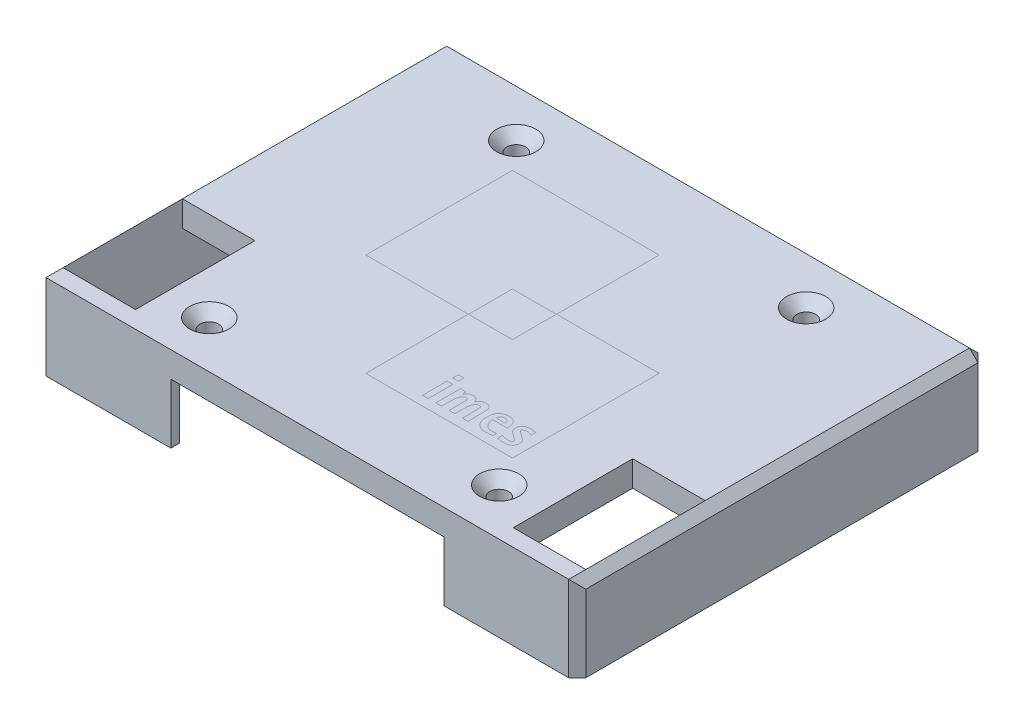
SolidWorks part; units mm, degrees
ref_plane "Front Plane" through (0, 0, 0) normal (0, 0, 1) x (1, 0, 0)
ref_plane "Top Plane" through (0, 0, 0) normal (0, 1, 0) x (1, 0, 0)
ref_plane "Right Plane" through (0, 0, 0) normal (1, 0, 0) x (0, 0, -1)
sketch "Sketch1" plane through (0, 0, 0) normal (0, 1, 0) x (1, 0, 0)
  line L1 (-31.65, -24) -> (31.65, -24)
  line L2 (-31.65, -24) -> (-31.65, 24)
  line L3 (-31.65, 24) -> (31.65, 24)
  line L4 (31.65, -24) -> (31.65, 24)
  line L5 (-31.65, -24) -> (31.65, 24) construction
  line L6 (-31.65, 24) -> (31.65, -24) construction
  line L7 (-17, -18.5) -> (17, -18.5) construction
  line L8 (-17, -18.5) -> (-17, 17.5) construction
  line L9 (-17, 17.5) -> (17, 17.5) construction
  line L10 (17, -18.5) -> (17, 17.5) construction
  line L11 (-17, -18.5) -> (17, 17.5) construction
  line L12 (-17, 17.5) -> (17, -18.5) construction
  point P0 (0, 0)
  point P6 (0, 0)
  point P11 (12.723, -13.4714)
  point P12 (0, -0.5)
  dimension "D1" = 63.3
  dimension "D2" = 48
  dimension "D3" = 36
  dimension "D4" = 34
  dimension "D5" = 0.5
extrude "Boss-Extrude1" add sketch "Sketch1" along normal blind 3
sketch "Sketch2" plane through (0, 0, 0) normal (0, -1, 0) x (1, 0, 0)
  line L0 (-16, 24) -> (-16, 23)
  line L1 (-31.65, 24) -> (31.65, 24) construction
  line L2 (-16, 23) -> (-30.65, 23)
  line L3 (-30.65, 23) -> (-30.65, -23)
  line L4 (-30.65, -23) -> (30.65, -23)
  line L5 (30.65, -23) -> (30.65, 23)
  line L6 (30.65, 23) -> (16, 23)
  line L7 (16, 23) -> (16, 24)
  line L8 (16, 24) -> (31.65, 24)
  line L9 (31.65, 24) -> (31.65, -24) construction
  line L10 (31.65, 24) -> (31.65, -24)
  line L11 (31.65, -24) -> (-31.65, -24)
  line L12 (-31.65, -24) -> (-31.65, 24)
  line L13 (-31.65, 24) -> (-16, 24)
  line L14 (-30.65, 23) -> (-31.65, 23) construction
  line L15 (30.65, 23) -> (31.65, 23) construction
  line L16 (-30.65, -23) -> (-30.65, -24) construction
  point P4 (-16.5638, 19.6362)
  dimension "D1" = 1
  dimension "D2" = 32
extrude "Boss-Extrude2" add sketch "Sketch2" along normal blind 7
sketch "Sketch3" plane through (0, 3, 0) normal (0, 1, 0) x (1, 0, 0)
  circle A0 centre (-17, 17.5) radius 1.1
  circle A1 centre (17, 17.5) radius 1.1
  circle A2 centre (17, -18.5) radius 1.1
  circle A3 centre (-17, -18.5) radius 1.1
  dimension "D1" = 2.2
extrude "Cut-Extrude1" cut sketch "Sketch3" against normal through all
chamfer "Chamfer1" distance 1.2 angle 45 4 edges at (-17, 3, 19.6) (17, 3, 19.6) (17, 3, -16.4) (-17, 3, -16.4)
chamfer "Chamfer2" distance 1 angle 45 8 edges at (31.65, -2, -24) (31.65, -2, 24) (31.65, 3, 0) (0, 0, -23) (-31.65, -2, -24) (-31.65, -2, 24) (-31.65, 3, 0) (0, 3, -24)
sketch "Sketch4" plane through (0, 3, 0) normal (0, 1, 0) x (1, 0, 0)
  line L0 (-30.65, 23) -> (-30.65, -24) construction
  line L1 (-30.65, -22) -> (-22.15, -22)
  line L2 (-30.65, -22) -> (-30.65, -8)
  line L3 (-30.65, -8) -> (-22.15, -8)
  line L4 (-22.15, -22) -> (-22.15, -8)
  line L5 (30.65, -22) -> (22.15, -22)
  line L6 (30.65, -22) -> (30.65, -8)
  line L7 (30.65, -8) -> (22.15, -8)
  line L8 (22.15, -22) -> (22.15, -8)
  line L9 (30.65, -24) -> (30.65, 23) construction
  line L10 (-31.65, -24) -> (31.65, -24) construction
  point P10 (-29.2539, -21.6399)
  point P13 (29.5211, -20.5044)
  dimension "D1" = 14
  dimension "D2" = 8.5
  dimension "D3" = 2
extrude "Cut-Extrude2" cut sketch "Sketch4" against normal up to surface (3 mm away) up to face at (-17, 0, 17.4)
sketch "Sketch12" plane through (-14.1896, 3, 15.0051) normal (0, 1, 0) x (1, 0, 0)
  line L0 (12.02, 6.0391) -> (12.02, 12.0491)
  line L1 (12.02, 12.0491) -> (6.01, 12.0491)
  line L2 (6.01, 12.0491) -> (0, 12.0491)
  line L3 (0, 12.0491) -> (0, 20.6494)
  line L4 (0, 20.6494) -> (0, 29.2497)
  line L5 (0, 29.2497) -> (8.6003, 29.2497)
  line L6 (8.6003, 29.2497) -> (17.2006, 29.2497)
  line L7 (17.2006, 29.2497) -> (17.2006, 23.2397)
  line L8 (17.2006, 23.2397) -> (17.2006, 17.2297)
  line L9 (17.2006, 17.2297) -> (23.2106, 17.2297)
  line L10 (23.2106, 17.2297) -> (29.2206, 17.2297)
  line L11 (29.2206, 17.2297) -> (29.2206, 8.6294)
  line L12 (29.2206, 8.6294) -> (29.2206, 0.0291)
  line L13 (29.2206, 0.0291) -> (20.6203, 0.0291)
  line L14 (20.6203, 0.0291) -> (12.02, 0.0291)
  line L15 (12.02, 0.0291) -> (12.02, 6.0391)
  line L16 (25.7389, 1.1532) -> (25.7863, 1.1689)
  line L17 (25.7863, 1.1689) -> (25.7863, 1.4025)
  line L18 (25.0287, 2.7649) -> (25.8736, 2.7649)
  line L19 (25.8736, 2.7649) -> (25.8734, 2.8886)
  line L20 (25.648, 1.1354) -> (25.7389, 1.1532)
  line L21 (25.2255, 3.2583) -> (25.241, 3.1432)
  line L22 (25.241, 3.1432) -> (24.7133, 3.1432)
  line L23 (27.9982, 3.7081) -> (27.9982, 3.9819)
  line L24 (27.9982, 3.9819) -> (27.7187, 4.0322)
  line L25 (18.2483, 2.5757) -> (18.2483, 4.0164)
  line L26 (18.2483, 4.0164) -> (17.9136, 4.0164)
  line L27 (17.9136, 4.0164) -> (17.5789, 4.0164)
  line L28 (17.5789, 4.0164) -> (17.5789, 2.5757)
  line L29 (17.5789, 2.5757) -> (17.5789, 1.1351)
  line L30 (17.5789, 1.1351) -> (17.9136, 1.1351)
  line L31 (17.9136, 1.1351) -> (18.2483, 1.1351)
  line L32 (18.2483, 1.1351) -> (18.2483, 2.5757)
  line L33 (20.5803, 3.3577) -> (20.6494, 3.2841)
  line L34 (20.6494, 3.2841) -> (20.6577, 2.2096)
  line L35 (20.6577, 2.2096) -> (20.666, 1.1351)
  line L36 (20.666, 1.1351) -> (20.9997, 1.1351)
  line L37 (20.9997, 1.1351) -> (21.3334, 1.1351)
  line L38 (21.3334, 1.1351) -> (21.3339, 1.8408)
  line L39 (22.2303, 2.1755) -> (22.2396, 1.1351)
  line L40 (22.2396, 1.1351) -> (22.559, 1.1351)
  line L41 (22.559, 1.1351) -> (22.8784, 1.1351)
  line L42 (22.8784, 1.1351) -> (22.8699, 2.3065)
  line L43 (21.3928, 3.6655) -> (21.2861, 3.5003)
  line L44 (21.2861, 3.5003) -> (21.2357, 3.6423)
  line L45 (19.8751, 3.7013) -> (19.7909, 3.5684)
  line L46 (19.7909, 3.5684) -> (19.7909, 3.7924)
  line L47 (19.7909, 3.7924) -> (19.7909, 4.0164)
  line L48 (19.7909, 4.0164) -> (19.4562, 4.0164)
  line L49 (19.4562, 4.0164) -> (19.1215, 4.0164)
  line L50 (19.1215, 4.0164) -> (19.1215, 2.5757)
  line L51 (19.1215, 2.5757) -> (19.1215, 1.1351)
  line L52 (19.1215, 1.1351) -> (19.4542, 1.1351)
  line L53 (19.4542, 1.1351) -> (19.7868, 1.1351)
  line L54 (19.7868, 1.1351) -> (19.7968, 1.9572)
  line L55 (18.2483, 4.9768) -> (18.2483, 5.297)
  line L56 (18.2483, 5.297) -> (17.9136, 5.297)
  line L57 (17.9136, 5.297) -> (17.5789, 5.297)
  line L58 (17.5789, 5.297) -> (17.5789, 4.9768)
  line L59 (17.5789, 4.9768) -> (17.5789, 4.6567)
  line L60 (17.5789, 4.6567) -> (17.9136, 4.6567)
  line L61 (17.9136, 4.6567) -> (18.2483, 4.6567)
  line L62 (18.2483, 4.6567) -> (18.2483, 4.9768)
  line L63 (17.1934, 14.6321) -> (17.2009, 17.2006)
  line L64 (17.2009, 17.2006) -> (14.625, 17.2006)
  line L65 (14.625, 17.2006) -> (12.0491, 17.2006)
  line L66 (12.0491, 17.2006) -> (12.0491, 14.6247)
  line L67 (12.0491, 14.6247) -> (12.0491, 12.0488)
  line L68 (12.0491, 12.0488) -> (14.6176, 12.0562)
  line L69 (14.6176, 12.0562) -> (17.186, 12.0637)
  line L70 (17.186, 12.0637) -> (17.1934, 14.6321)
  line L71 (12.0491, 12.0488) -> (12.02, 12.0491)
  line L72 (17.2006, 17.2297) -> (17.2009, 17.2006)
  spline S0 degree 3 poles (25.7863, 1.4025) (25.7863, 1.6064) (25.7803, 1.6337) (25.7389, 1.6179) knots 0 0 0 0 1 1 1 1
  spline S1 degree 3 poles (25.7389, 1.6179) (25.587, 1.5596) (25.4067, 1.5369) (25.182, 1.5477) knots 0 0 0 0 1 1 1 1
  spline S2 degree 3 poles (25.182, 1.5477) (24.9701, 1.5579) (24.9018, 1.574) (24.7719, 1.6448) knots 0 0 0 0 1 1 1 1
  spline S3 degree 3 poles (24.7719, 1.6448) (24.488, 1.7994) (24.2566, 2.1387) (24.1822, 2.5093) knots 0 0 0 0 1 1 1 1
  spline S4 degree 3 poles (24.1822, 2.5093) (24.1273, 2.7829) (24.0677, 2.7649) (25.0287, 2.7649) knots 0 0 0 0 1 1 1 1
  spline S5 degree 3 poles (25.8734, 2.8886) (25.8729, 3.2392) (25.7424, 3.6138) (25.5583, 3.793) knots 0 0 0 0 1 1 1 1
  spline S6 degree 3 poles (25.5583, 3.793) (25.4996, 3.8501) (25.373, 3.9332) (25.2769, 3.9775) knots 0 0 0 0 1 1 1 1
  spline S7 degree 3 poles (25.2769, 3.9775) (25.1202, 4.0499) (25.0694, 4.0582) (24.7821, 4.0591) knots 0 0 0 0 1 1 1 1
  spline S8 degree 3 poles (24.7821, 4.0591) (24.4065, 4.0602) (24.1955, 4.0067) (24.0064, 3.8625) knots 0 0 0 0 1 1 1 1
  spline S9 degree 3 poles (24.0064, 3.8625) (23.8219, 3.7218) (23.6994, 3.5436) (23.6255, 3.3087) knots 0 0 0 0 1 1 1 1
  spline S10 degree 3 poles (23.6255, 3.3087) (23.5401, 3.0369) (23.5333, 2.4213) (23.6126, 2.1246) knots 0 0 0 0 1 1 1 1
  spline S11 degree 3 poles (23.6126, 2.1246) (23.754, 1.595) (24.0702, 1.2522) (24.5378, 1.1211) knots 0 0 0 0 1 1 1 1
  spline S12 degree 3 poles (24.5378, 1.1211) (24.7199, 1.0701) (25.4148, 1.0791) (25.648, 1.1354) knots 0 0 0 0 1 1 1 1
  spline S13 degree 3 poles (24.1856, 3.1878) (24.1856, 3.279) (24.2674, 3.4234) (24.37, 3.5136) knots 0 0 0 0 1 1 1 1
  spline S14 degree 3 poles (24.37, 3.5136) (24.6849, 3.79) (25.1738, 3.6441) (25.2255, 3.2583) knots 0 0 0 0 1 1 1 1
  spline S15 degree 3 poles (24.7133, 3.1432) (24.2587, 3.1432) (24.1856, 3.1494) (24.1856, 3.1878) knots 0 0 0 0 1 1 1 1
  spline S16 degree 3 poles (27.518, 1.1163) (27.9551, 1.2328) (28.1726, 1.4956) (28.1719, 1.9063) knots 0 0 0 0 1 1 1 1
  spline S17 degree 3 poles (28.1719, 1.9063) (28.1712, 2.29) (28.0437, 2.4566) (27.4575, 2.8394) knots 0 0 0 0 1 1 1 1
  spline S18 degree 3 poles (27.4575, 2.8394) (27.0307, 3.118) (26.9214, 3.2196) (26.9214, 3.3377) knots 0 0 0 0 1 1 1 1
  spline S19 degree 3 poles (26.9214, 3.3377) (26.9214, 3.4973) (27.2248, 3.6361) (27.4808, 3.5937) knots 0 0 0 0 1 1 1 1
  spline S20 degree 3 poles (27.4808, 3.5937) (27.5493, 3.5823) (27.6887, 3.5418) (27.7907, 3.5036) knots 0 0 0 0 1 1 1 1
  spline S21 degree 3 poles (27.7907, 3.5036) (27.8926, 3.4655) (27.981, 3.4343) (27.9871, 3.4343) knots 0 0 0 0 1 1 1 1
  spline S22 degree 3 poles (27.9871, 3.4343) (27.9932, 3.4343) (27.9982, 3.5575) (27.9982, 3.7081) knots 0 0 0 0 1 1 1 1
  spline S23 degree 3 poles (27.7187, 4.0322) (26.902, 4.1793) (26.3391, 3.8638) (26.3402, 3.2597) knots 0 0 0 0 1 1 1 1
  spline S24 degree 3 poles (26.3402, 3.2597) (26.3409, 2.9035) (26.4961, 2.6967) (27.0386, 2.3289) knots 0 0 0 0 1 1 1 1
  spline S25 degree 3 poles (27.0386, 2.3289) (27.4511, 2.0494) (27.5616, 1.9453) (27.5616, 1.8364) knots 0 0 0 0 1 1 1 1
  spline S26 degree 3 poles (27.5616, 1.8364) (27.5616, 1.5487) (26.9564, 1.4944) (26.3902, 1.7312) knots 0 0 0 0 1 1 1 1
  spline S27 degree 3 poles (26.3902, 1.7312) (26.3436, 1.7506) (26.3393, 1.7272) (26.3393, 1.4583) knots 0 0 0 0 1 1 1 1
  spline S28 degree 3 poles (26.3393, 1.4583) (26.3393, 1.2434) (26.3491, 1.1637) (26.3756, 1.1623) knots 0 0 0 0 1 1 1 1
  spline S29 degree 3 poles (26.3756, 1.1623) (26.3957, 1.1613) (26.4906, 1.1427) (26.5867, 1.1211) knots 0 0 0 0 1 1 1 1
  spline S30 degree 3 poles (26.5867, 1.1211) (26.8148, 1.0697) (27.333, 1.067) (27.518, 1.1163) knots 0 0 0 0 1 1 1 1
  spline S31 degree 3 poles (19.7968, 1.9572) (19.8064, 2.7414) (19.8101, 2.7875) (19.8759, 2.9541) knots 0 0 0 0 1 1 1 1
  spline S32 degree 3 poles (19.8759, 2.9541) (19.9803, 3.2181) (20.0898, 3.3613) (20.2304, 3.4176) knots 0 0 0 0 1 1 1 1
  spline S33 degree 3 poles (20.2304, 3.4176) (20.3774, 3.4763) (20.4863, 3.4577) (20.5803, 3.3577) knots 0 0 0 0 1 1 1 1
  spline S34 degree 3 poles (21.3339, 1.8408) (21.3345, 2.5902) (21.3592, 2.8003) (21.4802, 3.0816) knots 0 0 0 0 1 1 1 1
  spline S35 degree 3 poles (21.4802, 3.0816) (21.5972, 3.3537) (21.8461, 3.5112) (22.0352, 3.4329) knots 0 0 0 0 1 1 1 1
  spline S36 degree 3 poles (22.0352, 3.4329) (22.2148, 3.3585) (22.2201, 3.3244) (22.2303, 2.1755) knots 0 0 0 0 1 1 1 1
  spline S37 degree 3 poles (22.8699, 2.3065) (22.8615, 3.459) (22.8603, 3.4803) (22.7943, 3.6235) knots 0 0 0 0 1 1 1 1
  spline S38 degree 3 poles (22.7943, 3.6235) (22.6738, 3.8851) (22.4769, 4.0334) (22.2077, 4.0653) knots 0 0 0 0 1 1 1 1
  spline S39 degree 3 poles (22.2077, 4.0653) (21.8939, 4.1025) (21.5738, 3.9454) (21.3928, 3.6655) knots 0 0 0 0 1 1 1 1
  spline S40 degree 3 poles (21.2357, 3.6423) (21.168, 3.8328) (21.0216, 3.9739) (20.8336, 4.0297) knots 0 0 0 0 1 1 1 1
  spline S41 degree 3 poles (20.8336, 4.0297) (20.4439, 4.1455) (20.0771, 4.0198) (19.8751, 3.7013) knots 0 0 0 0 1 1 1 1
extrude "Cut-Extrude3" cut sketch "Sketch12" against normal blind 0.6 contours L15 L14 L13 L12 L11 L10 L9 L8 L7 L6 L5 L4 L3 L2 L1 L0 S41 S40 L44 L43 S39 S38 S37 L42 L41 L40 L39 S36 S35 S34 L38 L37 L36 L35 L34 L33 S33 S32 S31 L54 L53 L52 L51 L50 L49 L48 L47 L46 L45 | S15 L22 L21 S14 S13 region at (6.9369, 3, 6.6307) region at (10.5355, 3, 11.6428)
extrude "Boss-Extrude3" add sketch "Sketch12<4>" against normal blind 0.6 separate body contours L15 L14 L13 L12 L11 L10 L9 L8 L7 L6 L5 L4 L3 L2 L1 L0 S41 S40 L44 L43 S39 S38 S37 L42 L41 L40 L39 S36 S35 S34 L38 L37 L36 L35 L34 L33 S33 S32 S31 L54 L53 L52 L51 L50 L49 L48 L47 L46 L45 | S15 L22 L21 S14 S13 region at (6.9369, 3, 6.6307) region at (10.5355, 3, 11.6428)
sketch "Sketch12<4>" plane through (-14.1896, 3, 15.0051) normal (0, 1, 0) x (1, 0, 0) same geometry as "Sketch12"
extrude "Cut-Extrude4" cut sketch "Sketch12<5>" against normal blind 0.6 contours L72 L8 L7 L6 L5 L4 L3 L2 L1 L71 L67 L66 L65 L64 region at (-6.183, 3, -6.2379)
sketch "Sketch12<5>" plane through (-14.1896, 3, 15.0051) normal (0, 1, 0) x (1, 0, 0) same geometry as "Sketch12"
extrude "Boss-Extrude4" add sketch "Sketch12<6>" against normal blind 0.6 separate body contours L72 L8 L7 L6 L5 L4 L3 L2 L1 L71 L67 L66 L65 L64 region at (-6.183, 3, -6.2379)
sketch "Sketch12<6>" plane through (-14.1896, 3, 15.0051) normal (0, 1, 0) x (1, 0, 0) same geometry as "Sketch12"
